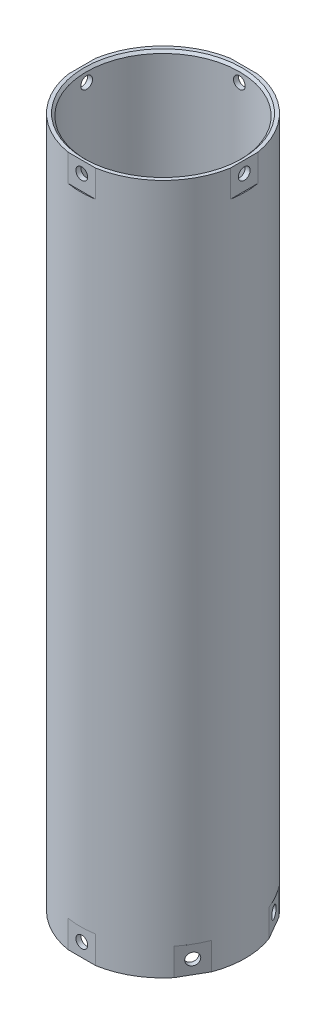
SolidWorks part; units mm, degrees
material "1060 Alloy"
ref_plane "Front Plane" through (0, 0, 0) normal (0, 0, 1) x (1, 0, 0)
ref_plane "Top Plane" through (0, 0, 0) normal (0, 1, 0) x (1, 0, 0)
ref_plane "Right Plane" through (0, 0, 0) normal (1, 0, 0) x (0, 0, -1)
sketch "Sketch2" plane through (0, 0, 0) normal (0, 0, 1) x (1, 0, 0)
  line L0 (0, 0) -> (0, 365.76) construction
  line L3 (41.275, 0) -> (44.45, 0)
  line L5 (41.275, 372.618) -> (44.45, 372.618)
  line L6 (44.45, 0) -> (44.45, 372.618)
  line L11 (41.275, 372.618) -> (41.275, 186.309)
  line L12 (41.275, 186.309) -> (41.2565, 186.2833)
  line L13 (41.275, 186.309) -> (41.275, 0)
  line L14 (0, -48.895) -> (0, 48.895) construction
  dimension "D3" = 3.175
  dimension "D4" = 372.618
revolve "Revolve1" add sketch "Sketch2" angle 360 about L0 region at (42.8625, 186.309, 0)
ref_axis "Axis1" through (0, -17.0472, 0) along (0, 1, 0)
ref_plane "Plane1" through (0, 7.366, 0) normal (0, -1, 0) x (-1, 0, 0)
ref_axis "Axis2" through (0, 7.366, 48.895) along (0, 0, -1)
hole_wizard "1/4 (0.25) Diameter Hole1" positions "3DSketch1" profile "Sketch3" hole size "1/4" standard "ANSI Inch" end condition up to next
sketch3d "3DSketch1"
  line L0 (0, 7.366, 48.895) -> (0, 7.366, -48.895) construction
  point P0 (0, 7.366, -44.45)
sketch "Sketch3" plane through (0, 7.366, -44.45) normal (1, 0, 0) x (0, 1, 0)
  line L0 (0, 0) -> (0, 3.175)
  line L1 (0, 3.175) -> (3.175, 3.175)
  line L2 (3.175, 3.175) -> (3.175, 0)
  line L5 (3.175, 0) -> (0, 0)
  line L11 (0, -6.35) -> (0, 107.95) construction
  dimension "Thru Hole Dia." = 6.35
  dimension "Thru Hole Depth" = 3.175
ref_plane "Plane2" through (0, 366.268, 0) normal (0, 1, 0) x (1, 0, 0)
ref_axis "Axis3" through (0, 366.268, -48.895) along (0, 0, 1)
sketch "Sketch4" plane through (0, 0, 0) normal (0, 0, 1) x (1, 0, 0)
  line L0 (0, -17.0472) -> (0, 357.9914) construction
  line L1 (0, 366.268) -> (-43.7642, 366.268)
  line L2 (0, 366.268) -> (0, 363.22)
  line L3 (0, 363.22) -> (-43.7642, 363.22)
  line L4 (-43.7642, 366.268) -> (-43.7642, 363.22)
  line L5 (48.1965, 366.268) -> (-48.1965, 366.268) construction
  dimension "D1" = 43.7642
  dimension "D2" = 3.048
revolve "Cut-Revolve2" [suppressed] cut sketch "Sketch4" angle 360 about axis through (0, -17.0472, 0) along (0, 1, 0)
hole_wizard "1/4 (0.25) Diameter Hole2" positions "3DSketch3" profile "Sketch6" hole size "1/4" standard "ANSI Inch"
sketch3d "3DSketch3"
  line L0 (0, 366.268, -48.895) -> (0, 366.268, 48.895) construction
  point P0 (0, 366.268, -44.45)
sketch "Sketch6" plane through (0, 366.268, -44.45) normal (1, 0, 0) x (0, 1, 0)
  line L0 (0, 0) -> (0, 5.2097)
  line L1 (0, 5.2097) -> (3.175, 3.302)
  line L2 (3.175, 3.302) -> (3.175, 0)
  line L5 (3.175, 0) -> (0, 0)
  line L10 (0, 5.2097) -> (-3.175, 3.302) construction
  line L11 (0, -6.35) -> (0, 107.95) construction
  dimension "Hole Dia." = 6.35
  dimension "Hole Depth" = 3.302
  dimension "Drill Angle" = 118
pattern_circular "CirPattern2" count 4 over 360 about axis through (0, -17.0472, 0) along (0, 1, 0) of "1/4 (0.25) Diameter Hole2" reverse direction yes
chamfer "Chamfer1" distance 1.27 angle 45 2 edges at (0, 0, -41.275) (0, 372.618, -41.275)
ref_plane "Plane3" through (0, 0, -44.45) normal (0, 0, -1) x (-1, 0, 0)
pattern_circular "CirPattern1" count 6 over 360 about axis through (0, -17.0472, 0) along (0, 1, 0) of "1/4 (0.25) Diameter Hole1"
sketch "Sketch7" plane through (0, 0, -44.45) normal (0, 0, -1) x (-1, 0, 0)
  line L1 (7.366, 0) -> (-7.366, 0)
  line L2 (7.366, 0) -> (7.366, 14.732)
  line L3 (7.366, 14.732) -> (-7.366, 14.732)
  line L4 (-7.366, 0) -> (-7.366, 14.732)
  circle A1 centre (0, 7.366) radius 3.175 construction
  dimension "D1" = 14.732
  dimension "D2" = 14.732
  dimension "D4" = 7.366
  dimension "D3" = 7.366
extrude "Cut-Extrude1" cut sketch "Sketch7" against normal blind 0.635
sketch "Sketch8" plane through (0, 0, -44.45) normal (0, 0, -1) x (-1, 0, 0)
  line L1 (8.255, 358.013) -> (-8.255, 358.013)
  line L2 (8.255, 358.013) -> (8.255, 374.523)
  line L3 (8.255, 374.523) -> (-8.255, 374.523)
  line L4 (-8.255, 358.013) -> (-8.255, 374.523)
  circle A1 centre (0, 366.268) radius 3.175 construction
  dimension "D1" = 8.255
  dimension "D2" = 8.255
  dimension "D3" = 16.51
  dimension "D4" = 16.51
extrude "Cut-Extrude2" cut sketch "Sketch8" against normal blind 0.635
pattern_circular "CirPattern4" count 6 over 360 about axis through (0, -17.0472, 0) along (0, 1, 0) of "Cut-Extrude1"
pattern_circular "CirPattern5" count 4 over 360 about axis through (0, -17.0472, 0) along (0, 1, 0) of "Cut-Extrude2"
